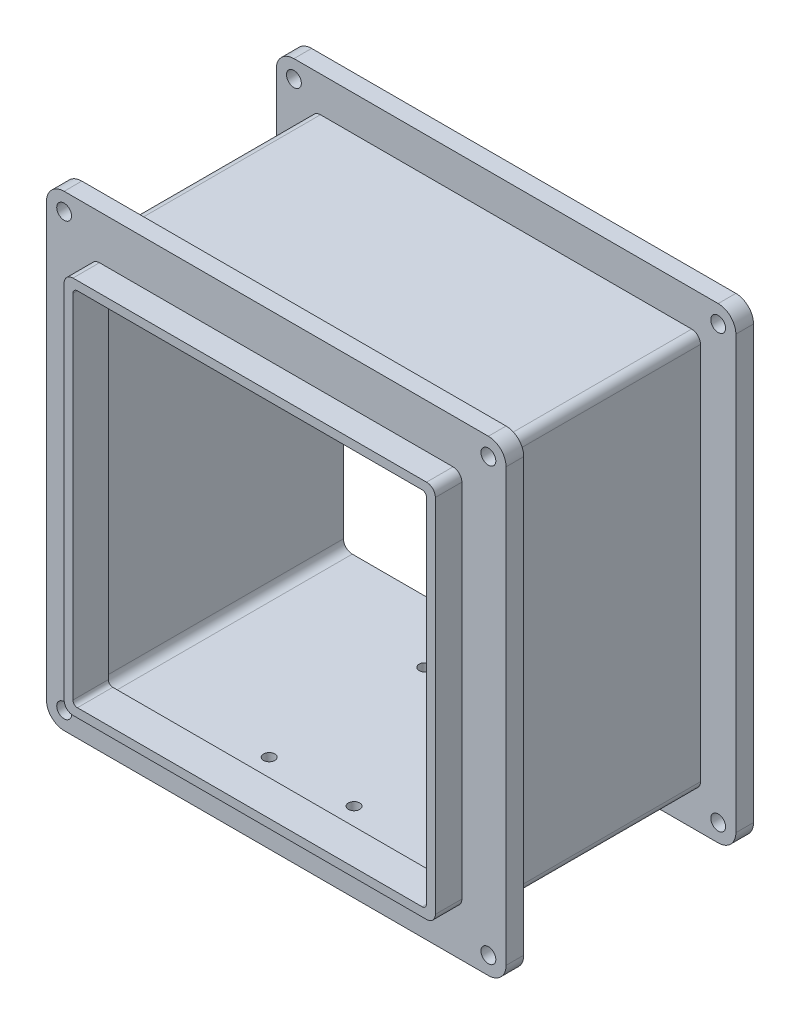
SolidWorks part; units mm, degrees
ref_plane "前视基准面" through (0, 0, 0) normal (0, 0, 1) x (1, 0, 0)
ref_plane "上视基准面" through (0, 0, 0) normal (0, 1, 0) x (1, 0, 0)
ref_plane "右视基准面" through (0, 0, 0) normal (1, 0, 0) x (0, 0, -1)
sketch "草图4" plane through (0, 0, 0) normal (0, 0, 1) x (1, 0, 0)
  line L1 (-105, -107.125) -> (105, -107.125)
  line L2 (-105, -107.125) -> (-105, 107.125)
  line L3 (-105, 107.125) -> (105, 107.125)
  line L4 (105, -107.125) -> (105, 107.125)
  line L5 (-105, -107.125) -> (105, 107.125) construction
  line L6 (-105, 107.125) -> (105, -107.125) construction
  line L7 (-110, -112.125) -> (110, -112.125)
  line L8 (-110, -112.125) -> (-110, 112.125)
  line L9 (-110, 112.125) -> (110, 112.125)
  line L10 (110, -112.125) -> (110, 112.125)
  line L11 (-110, -112.125) -> (110, 112.125) construction
  line L12 (-110, 112.125) -> (110, -112.125) construction
  point P0 (0, 0)
  point P6 (0, 0)
  dimension "D1" = 210
  dimension "D2" = 214.25
  dimension "D3" = 5
  dimension "D4" = 5
extrude "凸台-拉伸7" add sketch "草图4" along normal blind 120
sketch "草图7" plane through (0, 0, 0) normal (0, 0, -1) x (-1, 0, 0)
  line L0 (-110, 112.125) -> (110, 112.125) construction
  line L1 (130, 132.125) -> (-130, 132.125)
  line L2 (130, 132.125) -> (130, -132.125)
  line L3 (130, -132.125) -> (-130, -132.125)
  line L4 (-130, 132.125) -> (-130, -132.125)
  line L5 (130, 132.125) -> (-130, -132.125) construction
  line L6 (130, -132.125) -> (-130, 132.125) construction
  line L7 (-110, -112.125) -> (-110, 112.125) construction
  line L8 (105, -107.125) -> (-105, -107.125) construction
  line L9 (105, 107.125) -> (105, -107.125) construction
  line L10 (-105, 107.125) -> (105, 107.125) construction
  line L11 (-105, -107.125) -> (-105, 107.125) construction
  line L12 (105, -107.125) -> (-105, -107.125)
  line L13 (105, 107.125) -> (105, -107.125)
  line L14 (-105, 107.125) -> (105, 107.125)
  line L15 (-105, -107.125) -> (-105, 107.125)
  point P0 (0, 0)
  dimension "D1" = 20
  dimension "D2" = 20
extrude "凸台-拉伸8" add sketch "草图7" along normal blind 10
sketch "草图8" plane through (0, 0, 120) normal (0, 0, 1) x (1, 0, 0)
  line L1 (130, -132.125) -> (-130, -132.125)
  line L2 (130, -132.125) -> (130, 132.125)
  line L3 (130, 132.125) -> (-130, 132.125)
  line L4 (-130, -132.125) -> (-130, 132.125)
  line L5 (130, -132.125) -> (-130, 132.125) construction
  line L6 (130, 132.125) -> (-130, -132.125) construction
  line L7 (105, -107.125) -> (105, 107.125) construction
  line L8 (-105, -107.125) -> (105, -107.125) construction
  line L9 (-105, 107.125) -> (-105, -107.125) construction
  line L10 (105, 107.125) -> (-105, 107.125) construction
  line L11 (105, -107.125) -> (105, 107.125)
  line L12 (-105, -107.125) -> (105, -107.125)
  line L13 (-105, 107.125) -> (-105, -107.125)
  line L14 (105, 107.125) -> (-105, 107.125)
  point P0 (0, 0)
extrude "凸台-拉伸9" add sketch "草图8" along normal blind 10
fillet "圆角5" radius 5 8 edges at (-105, 107.125, 60) (-110, 112.125, 60) (105, -107.125, 60) (110, -112.125, 60) (-105, -107.125, 60) (-110, -112.125, 60) (110, 112.125, 60) (105, 107.125, 60)
fillet "圆角6" radius 10 8 edges at (130, 132.125, 125) (130, -132.125, 125) (-130, -132.125, 125) (-130, 132.125, 125) (-130, 132.125, -5) (-130, -132.125, -5) (130, -132.125, -5) (130, 132.125, -5)
hole_wizard "Ø8.4 (8.4) 直径孔1" positions "草图16" profile "草图17" hole size "Ø8.4" standard "GB" end condition through all
sketch "草图16" plane through (0, 0, -10) normal (0, 0, -1) x (-1, 0, 0)
  point P0 (120, -122.125)
  point P3 (120, 122.125)
  point P6 (-120, 122.125)
  point P9 (-120, -122.125)
sketch "草图17" plane through (-120, -122.125, -10) normal (1, 0, 0) x (0, 1, 0)
  line L0 (0, 0) -> (0, 140)
  line L1 (0, 140) -> (4.2, 140)
  line L2 (4.2, 140) -> (4.2, 0)
  line L5 (4.2, 0) -> (0, 0)
  line L11 (0, -6.35) -> (0, 107.95) construction
  dimension "通孔孔直径" = 8.4
  dimension "通孔孔深度" = 140
sketch "草图18" plane through (0, -112.125, 0) normal (0, -1, 0) x (1, 0, 0)
  line L0 (-120, 130) -> (120, 130) construction
  line L5 (105, 0) -> (105, 120) construction
  point P0 (-24, 110)
  point P1 (-24, 22)
  point P2 (24, 22)
  point P3 (24, 110)
  dimension "D1" = 48
  dimension "D2" = 48
  dimension "D3" = 88
  dimension "D4" = 88
  dimension "D5" = 100.2397
  dimension "D6" = 20
  dimension "D7" = 20
  dimension "D8" = 81
hole_wizard "Ø6.4 (6.4) 直径孔1" positions "草图21" profile "草图22" hole size "Ø6.4" standard "GB" end condition up to next
sketch "草图21" plane through (0, -112.125, 0) normal (0, -1, 0) x (-1, 0, 0)
  point P0 (24, -110)
  point P3 (-24, -110)
  point P6 (-24, -22)
  point P9 (24, -22)
sketch "草图22" plane through (-24, -112.125, 110) normal (1, 0, 0) x (0, 0, -1)
  line L0 (0, 0) -> (0, 5)
  line L1 (0, 5) -> (3.2, 5)
  line L2 (3.2, 5) -> (3.2, 0)
  line L5 (3.2, 0) -> (0, 0)
  line L11 (0, -6.35) -> (0, 107.95) construction
  dimension "通孔孔直径" = 6.4
  dimension "通孔孔深度" = 5
sketch "草图24" plane through (0, 0, 130) normal (0, 0, 1) x (1, 0, 0)
  line L0 (105, -102.125) -> (105, 102.125) construction
  line L1 (-100, -107.125) -> (100, -107.125) construction
  line L2 (-105, 102.125) -> (-105, -102.125) construction
  line L3 (100, 107.125) -> (-100, 107.125) construction
  line L4 (105, -102.125) -> (105, 102.125)
  line L5 (-100, -107.125) -> (100, -107.125)
  line L6 (-105, 102.125) -> (-105, -102.125)
  line L7 (100, 107.125) -> (-100, 107.125)
  line L9 (100, -102.125) -> (-100, -102.125)
  line L10 (100, -102.125) -> (100, 102.125)
  line L11 (100, 102.125) -> (-100, 102.125)
  line L12 (-100, -102.125) -> (-100, 102.125)
  line L13 (100, -102.125) -> (-100, 102.125) construction
  line L14 (100, 102.125) -> (-100, -102.125) construction
  arc A0 (105, 102.125) -> (100, 107.125) centre (100, 102.125) ccw construction
  arc A1 (100, -107.125) -> (105, -102.125) centre (100, -102.125) ccw construction
  arc A2 (-105, -102.125) -> (-100, -107.125) centre (-100, -102.125) ccw construction
  arc A3 (-100, 107.125) -> (-105, 102.125) centre (-100, 102.125) ccw construction
  arc A4 (105, 102.125) -> (100, 107.125) centre (100, 102.125) ccw
  arc A5 (100, -107.125) -> (105, -102.125) centre (100, -102.125) ccw
  arc A6 (-105, -102.125) -> (-100, -107.125) centre (-100, -102.125) ccw
  arc A7 (-100, 107.125) -> (-105, 102.125) centre (-100, 102.125) ccw
  point P12 (0, 0)
  dimension "D1" = 5
  dimension "D2" = 5
extrude "凸台-拉伸10" add sketch "草图24" along normal blind 15 separate body
sketch "草图25" plane through (0, 0, 130) normal (0, 0, -1) x (-1, 0, 0)
  line L0 (100, -102.125) -> (-100, -102.125) construction
  line L1 (-100, -102.125) -> (-100, 102.125) construction
  line L2 (100, 102.125) -> (100, -102.125) construction
  line L3 (-100, 102.125) -> (100, 102.125) construction
  line L4 (105, -102.125) -> (105, 102.125) construction
  line L5 (-100, -107.125) -> (100, -107.125) construction
  line L6 (-105, 102.125) -> (-105, -102.125) construction
  line L7 (100, 107.125) -> (-100, 107.125) construction
  line L8 (100, -102.125) -> (-100, -102.125)
  line L9 (-100, -102.125) -> (-100, 102.125)
  line L10 (100, 102.125) -> (100, -102.125)
  line L11 (-100, 102.125) -> (100, 102.125)
  line L12 (105, -102.125) -> (105, 102.125)
  line L13 (-100, -107.125) -> (100, -107.125)
  line L14 (-105, 102.125) -> (-105, -102.125)
  line L15 (100, 107.125) -> (-100, 107.125)
  arc A0 (105, 102.125) -> (100, 107.125) centre (100, 102.125) ccw construction
  arc A1 (100, -107.125) -> (105, -102.125) centre (100, -102.125) ccw construction
  arc A2 (-105, -102.125) -> (-100, -107.125) centre (-100, -102.125) ccw construction
  arc A3 (-100, 107.125) -> (-105, 102.125) centre (-100, 102.125) ccw construction
  arc A4 (105, 102.125) -> (100, 107.125) centre (100, 102.125) ccw
  arc A5 (100, -107.125) -> (105, -102.125) centre (100, -102.125) ccw
  arc A6 (-105, -102.125) -> (-100, -107.125) centre (-100, -102.125) ccw
  arc A7 (-100, 107.125) -> (-105, 102.125) centre (-100, 102.125) ccw
extrude "凸台-拉伸11" add sketch "草图25" along normal blind 5
fillet "圆角7" radius 2.5 12 edges at (103.5355, -105.6605, 125) (105, 0, 125) (103.5355, 105.6605, 125) (0, 107.125, 125) (-103.5355, 105.6605, 125) (-105, 0, 125) (-103.5355, -105.6605, 125) (0, -107.125, 125) (-100, -102.125, 135) (-100, 102.125, 135) (100, 102.125, 135) (100, -102.125, 135)
sketch "草图26" plane through (0, 0, -10) normal (0, 0, -1) x (-1, 0, 0)
  line L0 (-100, 107.125) -> (100, 107.125) construction
  line L1 (108, -110.125) -> (-108, -110.125)
  line L2 (108, -110.125) -> (108, 110.125)
  line L3 (108, 110.125) -> (-108, 110.125)
  line L4 (-108, -110.125) -> (-108, 110.125)
  line L5 (108, -110.125) -> (-108, 110.125) construction
  line L6 (108, 110.125) -> (-108, -110.125) construction
  line L7 (-105, 102.125) -> (-105, -102.125) construction
  line L8 (-100, -107.125) -> (100, -107.125) construction
  line L9 (105, -102.125) -> (105, 102.125) construction
  line L10 (100, -107.125) -> (-100, -107.125) construction
  line L11 (-105, -102.125) -> (-105, 102.125) construction
  line L12 (-100, -107.125) -> (100, -107.125)
  line L13 (105, -102.125) -> (105, 102.125)
  line L14 (100, -107.125) -> (-100, -107.125)
  line L15 (-105, -102.125) -> (-105, 102.125)
  line L16 (-100, 107.125) -> (100, 107.125)
  arc A0 (105, 102.125) -> (100, 107.125) centre (100, 102.125) ccw construction
  arc A1 (100, -107.125) -> (105, -102.125) centre (100, -102.125) ccw construction
  arc A2 (-105, -102.125) -> (-100, -107.125) centre (-100, -102.125) ccw construction
  arc A3 (-100, 107.125) -> (-105, 102.125) centre (-100, 102.125) ccw construction
  arc A4 (105, 102.125) -> (100, 107.125) centre (100, 102.125) ccw
  arc A5 (100, -107.125) -> (105, -102.125) centre (100, -102.125) ccw
  arc A6 (-105, -102.125) -> (-100, -107.125) centre (-100, -102.125) ccw
  arc A7 (-100, 107.125) -> (-105, 102.125) centre (-100, 102.125) ccw
  point P0 (0, 0)
  line M14 (105, 102.125) -> (105, -102.125)
  arc M15 (105, -102.125) -> (100, -107.125) centre (100, -102.125) cw
  line M16 (100, -107.125) -> (-100, -107.125)
  arc M17 (-100, -107.125) -> (-105, -102.125) centre (-100, -102.125) cw
  line M18 (-105, -102.125) -> (-105, 102.125)
  arc M19 (-105, 102.125) -> (-100, 107.125) centre (-100, 102.125) cw
  line M20 (-100, 107.125) -> (100, 107.125)
  arc M21 (100, 107.125) -> (105, 102.125) centre (100, 102.125) cw
  dimension "D1" = 3
  dimension "D2" = 3
extrude "凸台-拉伸12" add sketch "草图26" along normal blind 3 contours L4 L1 L2 L3 M21 M14 M15 M16 M17 M18 M19 M20 region at (0, -109.8165, -10)
fillet "圆角8" radius 5 4 edges at (-108, -110.125, -11.5) (108, -110.125, -11.5) (108, 110.125, -11.5) (-108, 110.125, -11.5)
